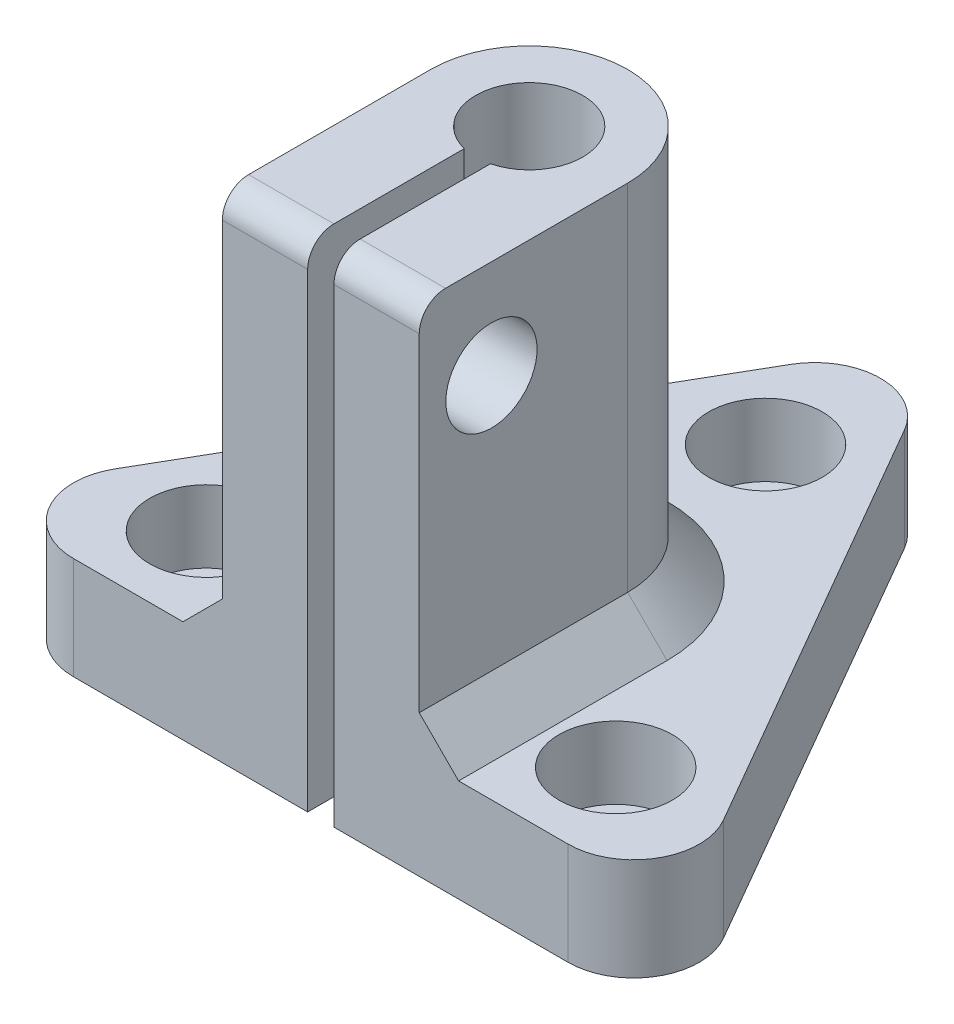
SolidWorks part; units mm, degrees
ref_plane "Plan de face" through (0, 0, 0) normal (0, 0, 1) x (1, 0, 0)
ref_plane "Plan de dessus" through (0, 0, 0) normal (0, 1, 0) x (1, 0, 0)
ref_plane "Plan de droite" through (0, 0, 0) normal (1, 0, 0) x (0, 0, -1)
sketch "Esquisse5" plane through (0, 0, 0) normal (0, 1, 0) x (1, 0, 0)
  line L0 (-27.5, -15.8771) -> (27.5, -15.8771)
  line L1 (27.5, -15.8771) -> (0, 31.7543)
  line L2 (0, 31.7543) -> (-27.5, -15.8771)
  line L3 (13.75, 7.9386) -> (-27.5, -15.8771) construction
  line L4 (-13.75, 7.9386) -> (27.5, -15.8771) construction
  circle A0 centre (0, 18) radius 2.575
  circle A1 centre (-15.5885, -9) radius 2.575
  circle A2 centre (15.5885, -9) radius 2.575
  dimension "D1" = 5.15
  dimension "D2" = 18
  dimension "D3" = 18
  dimension "D4" = 18
  dimension "D5" = 55
extrude "Boss.-Extru.2" add sketch "Esquisse5" along normal blind 7.8
sketch "Esquisse6" plane through (0, 7.8, 0) normal (0, 1, 0) x (1, 0, 0)
  circle A0 centre (0, 0) radius 7.5
  dimension "D1" = 15
extrude "Boss.-Extru.3" add sketch "Esquisse6" along normal blind 30
sketch "Esquisse13" plane through (0, 37.8, 0) normal (0, 1, 0) x (1, 0, 0)
  line L1 (-7.5, 0) -> (-7.5, -15.8771)
  line L2 (7.5, 0) -> (7.5, -15.8771)
  line L3 (-7.5, -15.8771) -> (7.5, -15.8771)
  line L4 (-27.5, -15.8771) -> (27.5, -15.8771) construction
  circle A0 centre (0, 0) radius 7.5 construction
  circle A1 centre (0, 0) radius 7.5 construction
  arc A2 (-7.5, 0) -> (7.5, 0) centre (0, 0) ccw
  point P8 (0, -15.8771)
  point P13 (0, 0)
  point P14 (-6, -4.5)
extrude "Boss.-Extru.6" add sketch "Esquisse13" against normal up to surface (30 mm away) up to face at (0, 7.8, 7.5)
sketch "Esquisse14" plane through (0, 37.8, 0) normal (0, 1, 0) x (1, 0, 0)
  circle A0 centre (0, 0) radius 4.075
  dimension "D1" = 8.15
extrude "Enlèv. mat.-Extru.4" cut sketch "Esquisse14" against normal through all
sketch "Esquisse15" plane through (0, 37.8, 0) normal (0, 1, 0) x (1, 0, 0)
  line L1 (-1, -3.9504) -> (-1, -15.8771)
  line L2 (1, -3.9504) -> (1, -15.8771)
  line L3 (-1, -15.8771) -> (1, -15.8771)
  line L4 (-7.5, -15.8771) -> (7.5, -15.8771) construction
  circle A0 centre (0, 0) radius 4.075 construction
  arc A1 (-1, -3.9504) -> (1, -3.9504) centre (0, 0) ccw
  point P9 (1, -3.9504)
  dimension "D1" = 2
extrude "Enlèv. mat.-Extru.5" cut sketch "Esquisse15" against normal through all
fillet "Congé2" radius 5 3 edges at (0, 3.9, -31.7543) (-27.5, 3.9, 15.8771) (27.5, 3.9, 15.8771)
sketch "Esquisse17" plane through (7.5, 0, 0) normal (1, 0, 0) x (0, 0, -1)
  line L0 (-15.8771, 37.8) -> (0, 37.8) construction
  line L1 (-15.8771, 7.8) -> (-15.8771, 37.8) construction
  circle A0 centre (-10.3771, 30.3) radius 2.05
  dimension "D1" = 4.1
  dimension "D2" = 7.5
  dimension "D3" = 5.5
extrude "Enlèv. mat.-Extru.6" cut sketch "Esquisse17" against normal through all
sketch "Esquisse18" plane through (-7.5, 0, 0) normal (-1, 0, 0) x (0, 0, 1)
  line L0 (0, 37.8) -> (15.8771, 37.8) construction
  line L1 (12.4123, 33.825) -> (8.342, 33.825)
  line L2 (8.342, 33.825) -> (6.3068, 30.3)
  line L3 (6.3068, 30.3) -> (8.342, 26.775)
  line L4 (8.342, 26.775) -> (12.4123, 26.775)
  line L5 (12.4123, 26.775) -> (14.4475, 30.3)
  line L6 (14.4475, 30.3) -> (12.4123, 33.825)
  circle A0 centre (10.3771, 30.3) radius 3.525 construction
  dimension "D1" = 7.05
extrude "Enlèv. mat.-Extru.7" cut sketch "Esquisse18" against normal blind 3.25
chamfer "Chanfrein1" distance 3 angle 45 3 edges at (0, 7.8, -7.5) (7.5, 7.8, 7.9386) (-7.5, 7.8, 7.9386)
sketch "Esquisse20" plane through (7.5, 0, 0) normal (1, 0, 0) x (0, 0, -1)
  circle A0 centre (-10.3771, 30.3) radius 3.475
  dimension "D1" = 6.95
extrude "Enlèv. mat.-Extru.9" cut sketch "Esquisse20" against normal blind 4.97
fillet "Congé3" radius 2 2 edges at (4.25, 37.8, 15.8771) (-4.25, 37.8, 15.8771)
sketch "Esquisse19" plane through (0, 7.8, 0) normal (0, 1, 0) x (1, 0, 0)
  circle A0 centre (0, 18) radius 4.325
  circle A1 centre (-15.5885, -9) radius 4.325
  circle A2 centre (15.5885, -9) radius 4.325
  dimension "D1" = 8.65
extrude "Enlèv. mat.-Extru.8" cut sketch "Esquisse19" against normal blind 5.5
